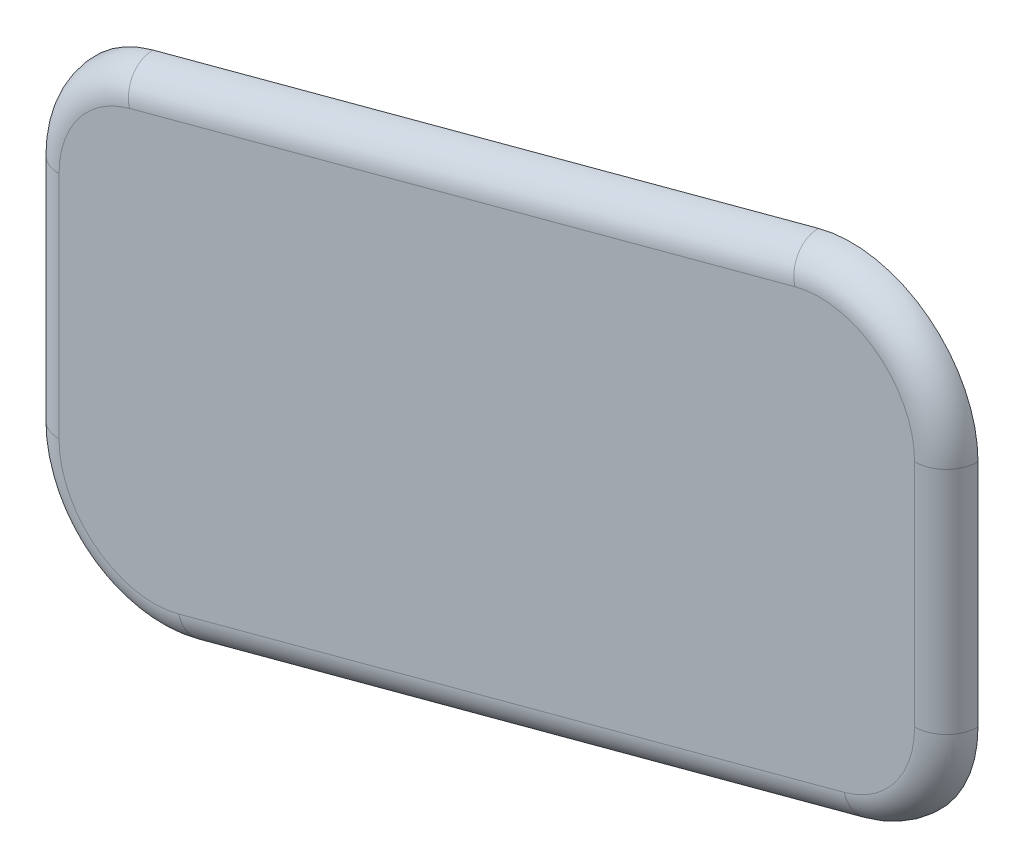
SolidWorks part; units mm, degrees
ref_plane "Спереди" through (0, 0, 0) normal (0, 0, 1) x (1, 0, 0)
ref_plane "Сверху" through (0, 0, 0) normal (0, 1, 0) x (1, 0, 0)
ref_plane "Справа" through (0, 0, 0) normal (1, 0, 0) x (0, 0, -1)
sketch "Эскиз1" plane through (0, 0, 0) normal (0, 0, 1) x (1, 0, 0)
  line L1 (0, 0) -> (29, 7.7705)
  line L2 (0, 0) -> (0, 15.5291)
  line L3 (0, 15.5291) -> (29, 23.2997)
  line L4 (29, 7.7705) -> (29, 23.2997)
  dimension "D1" = 75
  dimension "D2" = 29
  dimension "D3" = 15
extrude "Бобышка-Вытянуть1" add sketch "Эскиз1" along normal blind 1
fillet "Скругление1" radius 4 4 edges at (0, 15.5291, 0.5) (0, 0, 0.5) (29, 7.7705, 0.5) (29, 23.2997, 0.5)
fillet "Скругление2" radius 1 8 edges at (27.435, 21.2602, 1) (29, 14.4633, 1) (28.1734, 8.4048, 1) (15.5353, 4.1627, 1) (1.565, 2.0395, 1) (0, 8.8364, 1) (0.8266, 14.8949, 1) (13.4647, 19.137, 1)
